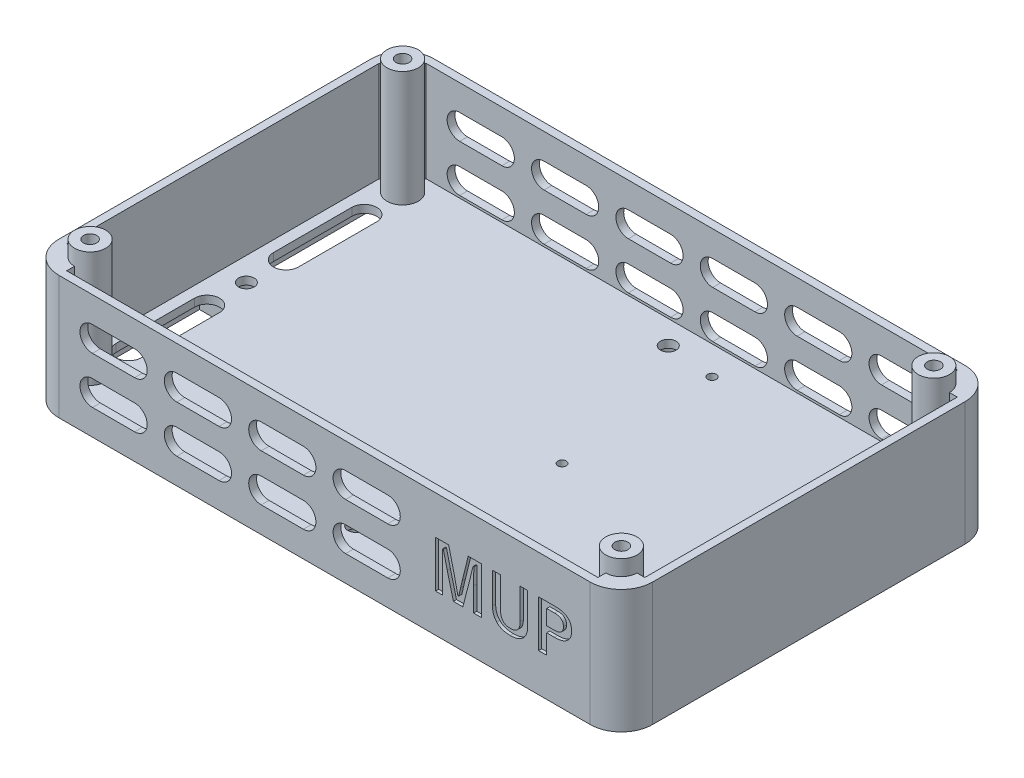
SolidWorks part; units mm, degrees
ref_plane "Front Plane" through (0, 0, 0) normal (0, 0, 1) x (1, 0, 0)
ref_plane "Top Plane" through (0, 0, 0) normal (0, 1, 0) x (1, 0, 0)
ref_plane "Right Plane" through (0, 0, 0) normal (1, 0, 0) x (0, 0, -1)
sketch "Sketch1" plane through (0, 94.5, 0) normal (0, 1, 0) x (1, 0, 0)
  line L0 (7.3241, -194.8914) -> (7.3241, -202.3914)
  line L1 (-7.6759, -194.8914) -> (-7.6759, -202.3914)
  line L2 (-85.1759, -152.3914) -> (-92.6759, -152.3914)
  line L3 (-84.9375, -137.4848) -> (-92.6759, -137.4848)
  line L4 (7.3241, -94.8914) -> (7.3241, -87.3914)
  line L5 (-7.6415, -94.1735) -> (-7.6759, -94.1891)
  line L7 (-7.6759, -94.8914) -> (-7.6759, -87.3914)
  line L9 (84.8241, -152.3914) -> (92.3241, -152.3914)
  line L10 (84.8241, -137.3914) -> (92.3241, -137.3914)
  line L16 (84.8241, -87.3914) -> (4.8241, -87.3914)
  line L17 (4.8241, -87.3914) -> (4.8241, -94.8914)
  line L18 (-5.1759, -94.8914) -> (-5.1759, -87.3914)
  line L19 (-5.1759, -87.3914) -> (-85.1759, -87.3914)
  line L20 (-92.6759, -94.8914) -> (-92.6759, -139.8914)
  line L21 (-92.6759, -139.8914) -> (-85.1759, -139.8914)
  line L22 (-85.1759, -149.8914) -> (-92.6759, -149.8914)
  line L23 (-92.6759, -149.8914) -> (-92.6759, -194.8914)
  line L24 (-85.1759, -202.3914) -> (-5.1759, -202.3914)
  line L25 (-5.1759, -202.3914) -> (-5.1759, -194.8914)
  line L26 (4.8241, -194.8914) -> (4.8241, -202.3914)
  line L27 (4.8241, -202.3914) -> (84.8241, -202.3914)
  line L28 (92.3241, -194.8914) -> (92.3241, -149.8914)
  line L29 (92.3241, -149.8914) -> (84.8241, -149.8914)
  line L30 (84.8241, -139.8914) -> (92.3241, -139.8914)
  line L31 (92.3241, -139.8914) -> (92.3241, -94.8914)
  line L32 (84.8241, -87.3914) -> (7.3241, -87.3914)
  line L35 (-7.6759, -87.3914) -> (-85.1759, -87.3914)
  line L36 (-92.6759, -94.8914) -> (-92.6759, -137.4848)
  line L39 (-92.6759, -152.3914) -> (-92.6759, -194.8914)
  line L40 (-85.1759, -202.3914) -> (-7.6759, -202.3914)
  line L43 (7.3241, -202.3914) -> (84.8241, -202.3914)
  line L44 (92.3241, -194.8914) -> (92.3241, -152.3914)
  line L47 (92.3241, -137.3914) -> (92.3241, -94.8914)
  circle A0 centre (84.8241, -144.8914) radius 5.5
  circle A1 centre (-0.1759, -194.8914) radius 5.5
  circle A2 centre (-85.1759, -144.8914) radius 5.5
  circle A3 centre (-0.1759, -94.8914) radius 5.5
  circle A5 centre (-0.1759, -194.8914) radius 7.5
  circle A7 centre (-0.1759, -94.8914) radius 7.5
  arc A8 (92.3241, -94.8914) -> (84.8241, -87.3914) centre (84.8241, -94.8914) ccw
  arc A9 (-5.1759, -94.8914) -> (4.8241, -94.8914) centre (-0.1759, -94.8914) ccw
  arc A10 (-85.1759, -87.3914) -> (-92.6759, -94.8914) centre (-85.1759, -94.8914) ccw
  arc A11 (-85.1759, -149.8914) -> (-85.1759, -139.8914) centre (-85.1759, -144.8914) ccw
  arc A12 (-92.6759, -194.8914) -> (-85.1759, -202.3914) centre (-85.1759, -194.8914) ccw
  arc A13 (4.8241, -194.8914) -> (-5.1759, -194.8914) centre (-0.1759, -194.8914) ccw
  arc A14 (84.8241, -202.3914) -> (92.3241, -194.8914) centre (84.8241, -194.8914) ccw
  arc A15 (84.8241, -139.8914) -> (84.8241, -149.8914) centre (84.8241, -144.8914) ccw
  arc A16 (92.3241, -94.8914) -> (84.8241, -87.3914) centre (84.8241, -94.8914) ccw
  arc A18 (-85.1759, -87.3914) -> (-92.6759, -94.8914) centre (-85.1759, -94.8914) ccw
  arc A20 (-92.6759, -194.8914) -> (-85.1759, -202.3914) centre (-85.1759, -194.8914) ccw
  arc A22 (84.8241, -202.3914) -> (92.3241, -194.8914) centre (84.8241, -194.8914) ccw
  circle A24 centre (84.8241, -144.8914) radius 7.5
  circle A25 centre (-85.1759, -144.8914) radius 7.5
  arc A26 (-88.9375, -133.4848) -> (-80.9375, -133.4848) centre (-84.9375, -133.4848) ccw construction
  point P51 (0, 0)
  line M25 (84.8241, -84.8914) -> (-85.1759, -84.8914)
  arc M26 (-85.1759, -84.8914) -> (-95.1759, -94.8914) centre (-85.1759, -94.8914) ccw
  line M27 (-95.1759, -94.8914) -> (-95.1759, -194.8914)
  arc M28 (-95.1759, -194.8914) -> (-85.1759, -204.8914) centre (-85.1759, -194.8914) ccw
  line M29 (-85.1759, -204.8914) -> (84.8241, -204.8914)
  arc M30 (84.8241, -204.8914) -> (94.8241, -194.8914) centre (84.8241, -194.8914) ccw
  line M31 (94.8241, -194.8914) -> (94.8241, -94.8914)
  arc M32 (94.8241, -94.8914) -> (84.8241, -84.8914) centre (84.8241, -94.8914) ccw
  line M33 (4.8241, -202.3914) -> (4.8241, -194.8914)
  line M35 (-5.1759, -194.8914) -> (-5.1759, -202.3914)
  line M36 (-5.1759, -202.3914) -> (-85.1759, -202.3914)
  arc M37 (-85.1759, -202.3914) -> (-92.6759, -194.8914) centre (-85.1759, -194.8914) cw
  line M38 (-92.6759, -194.8914) -> (-92.6759, -149.8914)
  line M39 (-92.6759, -149.8914) -> (-85.1759, -149.8914)
  line M41 (-85.1759, -139.8914) -> (-92.6759, -139.8914)
  line M42 (-92.6759, -139.8914) -> (-92.6759, -94.8914)
  arc M43 (-92.6759, -94.8914) -> (-85.1759, -87.3914) centre (-85.1759, -94.8914) cw
  line M44 (-85.1759, -87.3914) -> (-5.1759, -87.3914)
  line M45 (-5.1759, -87.3914) -> (-5.1759, -94.8914)
  line M47 (4.8241, -94.8914) -> (4.8241, -87.3914)
  line M48 (4.8241, -87.3914) -> (84.8241, -87.3914)
  arc M49 (84.8241, -87.3914) -> (92.3241, -94.8914) centre (84.8241, -94.8914) cw
  line M50 (92.3241, -94.8914) -> (92.3241, -139.8914)
  line M51 (92.3241, -139.8914) -> (84.8241, -139.8914)
  line M53 (84.8241, -149.8914) -> (92.3241, -149.8914)
  line M54 (92.3241, -149.8914) -> (92.3241, -194.8914)
  arc M55 (92.3241, -194.8914) -> (84.8241, -202.3914) centre (84.8241, -194.8914) cw
  line M56 (84.8241, -202.3914) -> (4.8241, -202.3914)
  dimension "D2" = 11
  dimension "D1" = 0
extrude "Boss-Extrude1" add sketch "Sketch1" along normal blind 5 contours A25 A7 A24 A5 M32 M25 M26 M27 M28 M29 M30 M31 M41 M42 M43 M44 M45 M47 M48 M49 M50 M51 M53 M54 M55 M56 M33 M35 M36 M37 M38 M39 | A24 A0 M53 M51 | A24 A0 M53 M51 | A24 L9 M54 M53 | A24 L10 M51 M50 | A5 A1 M33 M35 | A5 A1 M35 M33 | A5 L0 M33 M56 | A5 L1 M36 M35 | A25 L2 M39 M38 | A25 L3 M42 M41 | A25 A2 M41 M39 | A25 A2 M41 M39 | A7 A3 M47 M45 | A7 A3 M47 M45 | A7 L4 M48 M47 | A7 L7 L5 M45 M44 region at (6.4889, 94.5, 197.872) region at (6.324, 94.5, 200.3464) region at (-6.6758, 94.5, 200.3464) region at (-0.1759, 94.5, 200.5378) region at (90.2791, 94.5, 151.3913) region at (77.5231, 94.5, 144.8914) region at (-90.631, 94.5, 151.3913) region at (90.2791, 94.5, 138.3915) region at (90.4705, 94.5, 144.8914) region at (-88.1565, 94.5, 151.5562) region at (-90.8224, 94.5, 144.8914) region at (-90.7288, 94.5, 138.4624) region at (6.324, 94.5, 89.4364) region at (-0.1759, 94.5, 102.1923) region at (-0.1759, 94.5, 89.245) region at (-6.675, 94.5, 89.432) region at (90.3061, 94.5, 89.4094)
sketch "Sketch2" plane through (0, 99.5, 0) normal (0, 1, 0) x (1, 0, 0)
  line L4 (84.8241, -84.8914) -> (-85.1759, -84.8914)
  line L5 (-95.1759, -94.8914) -> (-95.1759, -194.8914)
  line L6 (-85.1759, -204.8914) -> (84.8241, -204.8914)
  line L7 (94.8241, -194.8914) -> (94.8241, -94.8914)
  line L8 (84.8241, -84.8914) -> (-85.1759, -84.8914)
  line L9 (-95.1759, -94.8914) -> (-95.1759, -194.8914)
  line L10 (-85.1759, -204.8914) -> (84.8241, -204.8914)
  line L11 (94.8241, -194.8914) -> (94.8241, -94.8914)
  arc A4 (94.8241, -94.8914) -> (84.8241, -84.8914) centre (84.8241, -94.8914) ccw
  arc A5 (-85.1759, -84.8914) -> (-95.1759, -94.8914) centre (-85.1759, -94.8914) ccw
  arc A6 (-95.1759, -194.8914) -> (-85.1759, -204.8914) centre (-85.1759, -194.8914) ccw
  arc A7 (84.8241, -204.8914) -> (94.8241, -194.8914) centre (84.8241, -194.8914) ccw
  arc A8 (94.8241, -94.8914) -> (84.8241, -84.8914) centre (84.8241, -94.8914) ccw
  arc A9 (-85.1759, -84.8914) -> (-95.1759, -94.8914) centre (-85.1759, -94.8914) ccw
  arc A10 (-95.1759, -194.8914) -> (-85.1759, -204.8914) centre (-85.1759, -194.8914) ccw
  arc A11 (84.8241, -204.8914) -> (94.8241, -194.8914) centre (84.8241, -194.8914) ccw
  dimension "D1" = 0
extrude "Boss-Extrude2" add sketch "Sketch2" along normal blind 2.5
sketch "Sketch5" plane through (0, 102, 0) normal (0, 1, 0) x (1, 0, 0)
  line L4 (-95.1759, -144.8914) -> (108.7771, -144.8914) construction
  line L5 (-95.1759, -94.8914) -> (-95.1759, -194.8914) construction
  line L8 (-80.9375, -132.4549) -> (-80.9375, -107.3914)
  line L9 (-88.9375, -107.3914) -> (-88.9375, -132.4549)
  line L10 (-88.9375, -182.3914) -> (-88.9375, -157.3279)
  line L11 (-80.9375, -157.3279) -> (-80.9375, -182.3914)
  line L16 (-85.1759, -89.8914) -> (-85.1759, -87.3914)
  line L17 (-90.1759, -94.8914) -> (-92.6759, -94.8914)
  line L18 (-92.6759, -194.8914) -> (-90.1759, -194.8914)
  line L19 (-85.1759, -199.8914) -> (-85.1759, -202.3914)
  line L20 (84.8241, -87.3914) -> (-85.1759, -87.3914)
  line L21 (-92.6759, -94.8914) -> (-92.6759, -194.8914)
  line L22 (-85.1759, -202.3914) -> (84.8241, -202.3914)
  line L23 (92.3241, -194.8914) -> (92.3241, -94.8914)
  line L24 (84.8241, -87.3914) -> (-85.1759, -87.3914)
  line L25 (-92.6759, -94.8914) -> (-92.6759, -194.8914)
  line L26 (-85.1759, -202.3914) -> (84.8241, -202.3914)
  line L27 (92.3241, -194.8914) -> (92.3241, -94.8914)
  line L28 (84.8241, -87.3914) -> (84.8241, -89.8914)
  line L29 (92.3241, -94.8914) -> (89.8241, -94.8914)
  line L30 (84.8241, -199.8914) -> (84.8241, -202.3914)
  line L31 (92.3241, -194.8914) -> (89.8241, -194.8914)
  circle A0 centre (-85.1759, -94.8914) radius 5
  circle A1 centre (84.8241, -94.8914) radius 5
  circle A2 centre (84.8241, -194.8914) radius 5
  circle A3 centre (-85.1759, -194.8914) radius 5
  arc A8 (-88.9375, -157.3279) -> (-80.9375, -157.3279) centre (-84.9375, -157.3279) cw
  arc A9 (-80.9375, -182.3914) -> (-88.9375, -182.3914) centre (-84.9375, -182.3914) cw
  arc A12 (-88.9375, -132.4549) -> (-80.9375, -132.4549) centre (-84.9375, -132.4549) ccw
  arc A13 (-80.9375, -107.3914) -> (-88.9375, -107.3914) centre (-84.9375, -107.3914) ccw
  arc A22 (92.3241, -94.8914) -> (84.8241, -87.3914) centre (84.8241, -94.8914) ccw
  arc A23 (-85.1759, -87.3914) -> (-92.6759, -94.8914) centre (-85.1759, -94.8914) ccw
  arc A24 (-92.6759, -194.8914) -> (-85.1759, -202.3914) centre (-85.1759, -194.8914) ccw
  arc A25 (84.8241, -202.3914) -> (92.3241, -194.8914) centre (84.8241, -194.8914) ccw
  arc A26 (92.3241, -94.8914) -> (84.8241, -87.3914) centre (84.8241, -94.8914) ccw
  arc A27 (-85.1759, -87.3914) -> (-92.6759, -94.8914) centre (-85.1759, -94.8914) ccw
  arc A28 (-92.6759, -194.8914) -> (-85.1759, -202.3914) centre (-85.1759, -194.8914) ccw
  arc A29 (84.8241, -202.3914) -> (92.3241, -194.8914) centre (84.8241, -194.8914) ccw
  point P14 (-84.9375, -103.3914)
  arc M14 (94.8241, -94.8914) -> (84.8241, -84.8914) centre (84.8241, -94.8914) ccw
  line M15 (84.8241, -84.8914) -> (-85.1759, -84.8914)
  arc M16 (-85.1759, -84.8914) -> (-95.1759, -94.8914) centre (-85.1759, -94.8914) ccw
  line M17 (-95.1759, -94.8914) -> (-95.1759, -194.8914)
  arc M18 (-95.1759, -194.8914) -> (-85.1759, -204.8914) centre (-85.1759, -194.8914) ccw
  line M19 (-85.1759, -204.8914) -> (84.8241, -204.8914)
  arc M20 (84.8241, -204.8914) -> (94.8241, -194.8914) centre (84.8241, -194.8914) ccw
  line M21 (94.8241, -194.8914) -> (94.8241, -94.8914)
  dimension "D1" = 18.5
  dimension "D2" = 2.5
extrude "Boss-Extrude4" add sketch "Sketch5" along normal blind 32 contours L4 L25 A27 L24 A26 L27 M17 M21 M14 M15 M16 | L4 L27 A29 L26 A28 L25 M17 M18 M19 M20 M21 | L16 A27 L17 A0 | A0 | A3 | L18 A28 L19 A3 | A2 | L30 A29 L31 A2 | A1 | L29 A26 L28 A1 region at (-93.1835, 102, 119.8914) region at (-93.9259, 102, 146.8839) region at (-89.2079, 102, 90.8595) region at (-89.2079, 102, 198.9233) region at (88.856, 102, 198.9233) region at (88.856, 102, 90.8595) region at (-85.1759, 102, 94.8914) region at (-85.1759, 102, 194.8914) region at (84.8241, 102, 194.8914) region at (84.8241, 102, 94.8914)
hole_wizard "Ø5.0 (5) Diameter Hole1" positions "Sketch6" profile "Sketch7" hole size "Ø5.0" standard "ISO"
sketch "Sketch6" plane through (0, 102, 0) normal (0, 1, 0) x (1, 0, 0)
  point P0 (-0.1759, -94.8914)
  point P3 (-85.1759, -144.8914)
  point P6 (84.8241, -144.8914)
  point P9 (-0.1759, -194.8914)
sketch "Sketch7" plane through (-0.1759, 102, 94.8914) normal (1, 0, 0) x (0, 0, 1)
  line L0 (0, 0) -> (0, 4.0022)
  line L1 (0, 4.0022) -> (2.5, 2.5)
  line L2 (2.5, 2.5) -> (2.5, 0)
  line L5 (2.5, 0) -> (0, 0)
  line L10 (0, 4.0022) -> (-2.5, 2.5) construction
  line L11 (0, -6.35) -> (0, 107.95) construction
  dimension "Hole Dia." = 5
  dimension "Hole Depth" = 2.5
  dimension "Drill Angle" = 118
sketch "Sketch8" plane through (0, 134, 0) normal (0, 1, 0) x (1, 0, 0)
  circle A0 centre (-85.1759, -194.8914) radius 5
  circle A1 centre (-85.1759, -94.8914) radius 5
  circle A2 centre (84.8241, -94.8914) radius 5
  circle A3 centre (84.8241, -194.8914) radius 5
extrude "Boss-Extrude5" add sketch "Sketch8" along normal blind 5
hole_wizard "Tap Drill for M5 Tap1" positions "Sketch9" profile "Sketch10" hole size "M5" standard "ISO"
sketch "Sketch9" plane through (0, 139, 0) normal (0, 1, 0) x (1, 0, 0)
  point P0 (-85.1759, -94.8914)
  point P3 (-85.1759, -194.8914)
  point P6 (84.8241, -94.8914)
  point P9 (84.8241, -194.8914)
sketch "Sketch10" plane through (-85.1759, 139, 94.8914) normal (1, 0, 0) x (0, 0, 1)
  line L0 (0, 0) -> (0, 21.2618)
  line L1 (0, 21.2618) -> (2.1, 20)
  line L2 (2.1, 20) -> (2.1, 0)
  line L5 (2.1, 0) -> (0, 0)
  line L10 (0, 21.2618) -> (-2.1, 20) construction
  line L11 (0, -6.35) -> (0, 107.95) construction
  dimension "Hole Dia." = 4.2
  dimension "Hole Depth" = 20
  dimension "Drill Angle" = 118
sketch "Sketch11" plane through (0, 102, 0) normal (0, 1, 0) x (1, 0, 0)
  line L2 (-92.6759, -144.8914) -> (-43.1546, -144.8914) construction
  line L3 (-92.6759, -94.8914) -> (-92.6759, -194.8914) construction
  line L6 (-81.1408, -132.2653) -> (-81.1408, -107.2017)
  line L7 (-89.1408, -107.2017) -> (-89.1408, -132.2653)
  line L8 (-89.1408, -182.5811) -> (-89.1408, -157.5175)
  line L9 (-81.1408, -157.5175) -> (-81.1408, -182.5811)
  arc A2 (-81.1408, -182.5811) -> (-89.1408, -182.5811) centre (-85.1408, -182.5811) cw
  arc A3 (-89.1408, -157.5175) -> (-81.1408, -157.5175) centre (-85.1408, -157.5175) cw
  arc A6 (-89.1408, -132.2653) -> (-81.1408, -132.2653) centre (-85.1408, -132.2653) ccw
  arc A7 (-81.1408, -107.2017) -> (-89.1408, -107.2017) centre (-85.1408, -107.2017) ccw
extrude "Cut-Extrude2" cut sketch "Sketch11" against normal blind 2.5
sketch "Sketch12" plane through (0, 102, 0) normal (0, 1, 0) x (1, 0, 0)
  circle A4 centre (19.3504, -155.4853) radius 1.1
  circle A5 centre (77.3504, -155.4853) radius 1.1
  circle A6 centre (77.3504, -113.9352) radius 1.1
  circle A7 centre (19.3504, -113.9352) radius 1.1
  point P1 (19.3504, -113.9352)
  point P3 (77.3504, -113.9352)
  point P5 (77.3504, -155.4853)
  point P7 (19.3504, -155.4853)
sketch "Sketch16" plane through (0, 102, 0) normal (0, 1, 0) x (1, 0, 0)
  line L0 (92.3241, -194.8914) -> (92.3241, -94.8914) construction
  line L1 (74.7241, -101.3914) -> (16.7241, -101.3914) construction
  line L2 (74.7241, -101.3914) -> (74.7241, -149.3914) construction
  line L3 (74.7241, -149.3914) -> (16.7241, -149.3914) construction
  line L4 (16.7241, -101.3914) -> (16.7241, -149.3914) construction
  line L5 (84.8241, -87.3914) -> (-85.1759, -87.3914) construction
  dimension "D1" = 48
  dimension "D2" = 58
  dimension "D3" = 17.6
  dimension "D4" = 14
sketch "Sketch17" plane through (0, 102, 0) normal (0, 1, 0) x (1, 0, 0)
  circle A0 centre (15.4697, -144.5267) radius 1.35
  circle A1 centre (15.4697, -96.5267) radius 1.4045
  circle A2 centre (73.4697, -144.5267) radius 1.35
  circle A3 centre (73.4697, -96.5267) radius 1.35
extrude "Cut-Extrude3" cut sketch "Sketch17" against normal blind 2.5
sketch "Sketch18" plane through (0, 0, 204.8914) normal (0, 0, 1) x (1, 0, 0)
  line L2 (-74.4259, 117.75) -> (-60.9259, 117.75)
  line L3 (-60.9259, 125.75) -> (-74.4259, 125.75)
  line L4 (-85.1759, 134) -> (84.8241, 134) construction
  line L5 (-33.9259, 125.75) -> (-47.4259, 125.75)
  line L6 (-47.4259, 117.75) -> (-33.9259, 117.75)
  line L7 (-6.9259, 125.75) -> (-20.4259, 125.75)
  line L8 (-20.4259, 117.75) -> (-6.9259, 117.75)
  line L9 (20.0741, 125.75) -> (6.5741, 125.75)
  line L10 (6.5741, 117.75) -> (20.0741, 117.75)
  line L15 (-33.9259, 110.75) -> (-47.4259, 110.75)
  line L16 (-47.4259, 102.75) -> (-33.9259, 102.75)
  line L17 (-6.9259, 110.75) -> (-20.4259, 110.75)
  line L18 (-20.4259, 102.75) -> (-6.9259, 102.75)
  line L19 (20.0741, 110.75) -> (6.5741, 110.75)
  line L20 (6.5741, 102.75) -> (20.0741, 102.75)
  line L25 (-60.9259, 110.75) -> (-74.4259, 110.75)
  line L26 (-74.4259, 102.75) -> (-60.9259, 102.75)
  line L27 (-60.9259, 125.75) -> (-33.9259, 125.75) construction
  line L28 (-60.9259, 125.75) -> (-60.9259, 110.75) construction
  line L30 (47.0741, 125.75) -> (33.5741, 125.75) [skipped]
  line L31 (33.5741, 117.75) -> (47.0741, 117.75) [skipped]
  line L32 (74.0741, 125.75) -> (60.5741, 125.75) [skipped]
  line L33 (60.5741, 117.75) -> (74.0741, 117.75) [skipped]
  line L34 (47.0741, 110.75) -> (33.5741, 110.75) [skipped]
  line L35 (33.5741, 102.75) -> (47.0741, 102.75) [skipped]
  line L36 (74.0741, 110.75) -> (60.5741, 110.75) [skipped]
  line L37 (60.5741, 102.75) -> (74.0741, 102.75) [skipped]
  arc A2 (-60.9259, 117.75) -> (-60.9259, 125.75) centre (-60.9259, 121.75) ccw
  arc A3 (-74.4259, 125.75) -> (-74.4259, 117.75) centre (-74.4259, 121.75) ccw
  arc A4 (-33.9259, 117.75) -> (-33.9259, 125.75) centre (-33.9259, 121.75) ccw
  arc A5 (-47.4259, 125.75) -> (-47.4259, 117.75) centre (-47.4259, 121.75) ccw
  arc A6 (-6.9259, 117.75) -> (-6.9259, 125.75) centre (-6.9259, 121.75) ccw
  arc A7 (-20.4259, 125.75) -> (-20.4259, 117.75) centre (-20.4259, 121.75) ccw
  arc A8 (20.0741, 117.75) -> (20.0741, 125.75) centre (20.0741, 121.75) ccw
  arc A9 (6.5741, 125.75) -> (6.5741, 117.75) centre (6.5741, 121.75) ccw
  arc A14 (-33.9259, 102.75) -> (-33.9259, 110.75) centre (-33.9259, 106.75) ccw
  arc A15 (-47.4259, 110.75) -> (-47.4259, 102.75) centre (-47.4259, 106.75) ccw
  arc A16 (-6.9259, 102.75) -> (-6.9259, 110.75) centre (-6.9259, 106.75) ccw
  arc A17 (-20.4259, 110.75) -> (-20.4259, 102.75) centre (-20.4259, 106.75) ccw
  arc A18 (20.0741, 102.75) -> (20.0741, 110.75) centre (20.0741, 106.75) ccw
  arc A19 (6.5741, 110.75) -> (6.5741, 102.75) centre (6.5741, 106.75) ccw
  arc A24 (-60.9259, 102.75) -> (-60.9259, 110.75) centre (-60.9259, 106.75) ccw
  arc A25 (-74.4259, 110.75) -> (-74.4259, 102.75) centre (-74.4259, 106.75) ccw
  arc A26 (47.0741, 117.75) -> (47.0741, 125.75) centre (47.0741, 121.75) ccw [skipped]
  arc A27 (33.5741, 125.75) -> (33.5741, 117.75) centre (33.5741, 121.75) ccw [skipped]
  arc A28 (74.0741, 117.75) -> (74.0741, 125.75) centre (74.0741, 121.75) ccw [skipped]
  arc A29 (60.5741, 125.75) -> (60.5741, 117.75) centre (60.5741, 121.75) ccw [skipped]
  arc A30 (47.0741, 102.75) -> (47.0741, 110.75) centre (47.0741, 106.75) ccw [skipped]
  arc A31 (33.5741, 110.75) -> (33.5741, 102.75) centre (33.5741, 106.75) ccw [skipped]
  arc A32 (74.0741, 102.75) -> (74.0741, 110.75) centre (74.0741, 106.75) ccw [skipped]
  arc A33 (60.5741, 110.75) -> (60.5741, 102.75) centre (60.5741, 106.75) ccw [skipped]
  dimension "D1" = 8.25
  dimension "D4" = 90
  dimension "D5" = 27
  dimension "D2" = 6
  dimension "D3" = 2
extrude "Cut-Extrude4" cut sketch "Sketch18" against normal blind 2.5
sketch "Sketch19" plane through (0, 0, 84.8914) normal (0, 0, -1) x (-1, 0, 0)
  line L2 (-60.5741, 117.75) -> (-74.0741, 117.75)
  line L3 (-74.0741, 125.75) -> (-60.5741, 125.75)
  line L4 (-47.0741, 125.75) -> (-33.5741, 125.75)
  line L5 (-33.5741, 117.75) -> (-47.0741, 117.75)
  line L6 (-20.0741, 125.75) -> (-6.5741, 125.75)
  line L7 (-6.5741, 117.75) -> (-20.0741, 117.75)
  line L8 (6.9259, 125.75) -> (20.4259, 125.75)
  line L9 (20.4259, 117.75) -> (6.9259, 117.75)
  line L10 (33.9259, 125.75) -> (47.4259, 125.75)
  line L11 (47.4259, 117.75) -> (33.9259, 117.75)
  line L12 (60.9259, 125.75) -> (74.4259, 125.75)
  line L13 (74.4259, 117.75) -> (60.9259, 117.75)
  line L14 (-47.0741, 110.75) -> (-33.5741, 110.75)
  line L15 (-33.5741, 102.75) -> (-47.0741, 102.75)
  line L16 (-20.0741, 110.75) -> (-6.5741, 110.75)
  line L17 (-6.5741, 102.75) -> (-20.0741, 102.75)
  line L18 (6.9259, 110.75) -> (20.4259, 110.75)
  line L19 (20.4259, 102.75) -> (6.9259, 102.75)
  line L20 (33.9259, 110.75) -> (47.4259, 110.75)
  line L21 (47.4259, 102.75) -> (33.9259, 102.75)
  line L22 (60.9259, 110.75) -> (74.4259, 110.75)
  line L23 (74.4259, 102.75) -> (60.9259, 102.75)
  line L24 (-74.0741, 110.75) -> (-60.5741, 110.75)
  line L25 (-60.5741, 102.75) -> (-74.0741, 102.75)
  line L26 (-60.5741, 117.75) -> (-33.5741, 117.75) construction
  line L27 (-60.5741, 117.75) -> (-60.5741, 102.75) construction
  arc A2 (-60.5741, 117.75) -> (-60.5741, 125.75) centre (-60.5741, 121.75) ccw
  arc A3 (-74.0741, 125.75) -> (-74.0741, 117.75) centre (-74.0741, 121.75) ccw
  arc A4 (-33.5741, 117.75) -> (-33.5741, 125.75) centre (-33.5741, 121.75) ccw
  arc A5 (-47.0741, 125.75) -> (-47.0741, 117.75) centre (-47.0741, 121.75) ccw
  arc A6 (-6.5741, 117.75) -> (-6.5741, 125.75) centre (-6.5741, 121.75) ccw
  arc A7 (-20.0741, 125.75) -> (-20.0741, 117.75) centre (-20.0741, 121.75) ccw
  arc A8 (20.4259, 117.75) -> (20.4259, 125.75) centre (20.4259, 121.75) ccw
  arc A9 (6.9259, 125.75) -> (6.9259, 117.75) centre (6.9259, 121.75) ccw
  arc A10 (47.4259, 117.75) -> (47.4259, 125.75) centre (47.4259, 121.75) ccw
  arc A11 (33.9259, 125.75) -> (33.9259, 117.75) centre (33.9259, 121.75) ccw
  arc A12 (74.4259, 117.75) -> (74.4259, 125.75) centre (74.4259, 121.75) ccw
  arc A13 (60.9259, 125.75) -> (60.9259, 117.75) centre (60.9259, 121.75) ccw
  arc A14 (-33.5741, 102.75) -> (-33.5741, 110.75) centre (-33.5741, 106.75) ccw
  arc A15 (-47.0741, 110.75) -> (-47.0741, 102.75) centre (-47.0741, 106.75) ccw
  arc A16 (-6.5741, 102.75) -> (-6.5741, 110.75) centre (-6.5741, 106.75) ccw
  arc A17 (-20.0741, 110.75) -> (-20.0741, 102.75) centre (-20.0741, 106.75) ccw
  arc A18 (20.4259, 102.75) -> (20.4259, 110.75) centre (20.4259, 106.75) ccw
  arc A19 (6.9259, 110.75) -> (6.9259, 102.75) centre (6.9259, 106.75) ccw
  arc A20 (47.4259, 102.75) -> (47.4259, 110.75) centre (47.4259, 106.75) ccw
  arc A21 (33.9259, 110.75) -> (33.9259, 102.75) centre (33.9259, 106.75) ccw
  arc A22 (74.4259, 102.75) -> (74.4259, 110.75) centre (74.4259, 106.75) ccw
  arc A23 (60.9259, 110.75) -> (60.9259, 102.75) centre (60.9259, 106.75) ccw
  arc A24 (-60.5741, 102.75) -> (-60.5741, 110.75) centre (-60.5741, 106.75) ccw
  arc A25 (-74.0741, 110.75) -> (-74.0741, 102.75) centre (-74.0741, 106.75) ccw
  dimension "D3" = 90
  dimension "D4" = 27
  dimension "D1" = 6
  dimension "D2" = 2
extrude "Cut-Extrude5" cut sketch "Sketch19" against normal blind 2.5
sketch "Sketch20" plane through (0, 0, 204.8914) normal (0, 0, 1) x (1, 0, 0)
  line L0 (33.5741, 106.75) -> (74.0741, 106.75) construction
  text T0 "MUP" font "Yu Gothic" height in points 48
extrude "Cut-Extrude6" cut sketch "Sketch20" against normal blind 1
